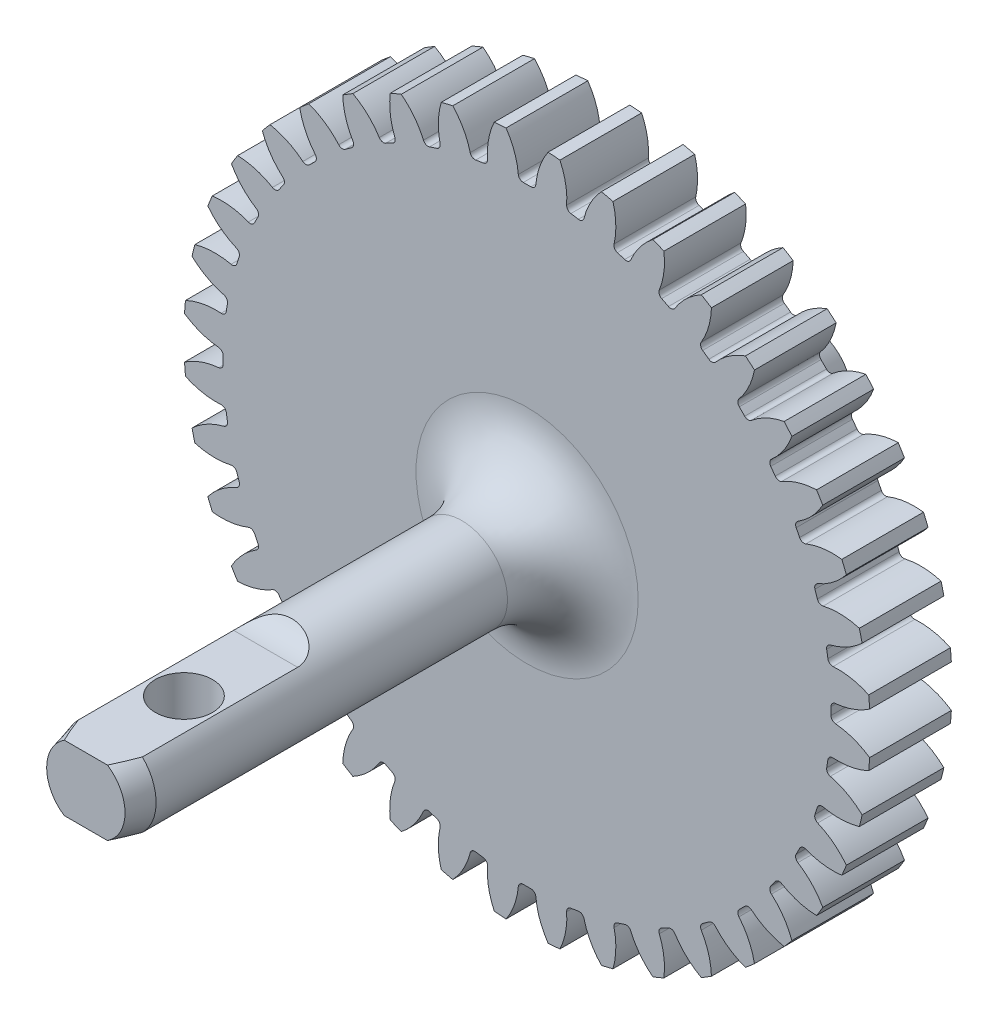
SolidWorks part; units mm, degrees
ref_plane "Front Plane" through (0, 0, 0) normal (0, 0, 1) x (1, 0, 0)
ref_plane "Top Plane" through (0, 0, 0) normal (0, 1, 0) x (1, 0, 0)
ref_plane "Right Plane" through (0, 0, 0) normal (1, 0, 0) x (0, 0, -1)
sketch "Sketch1" plane through (0, 0, 0) normal (0, 0, 1) x (1, 0, 0)
  circle A2 centre (0, 0) radius 20
  circle A3 centre (0, 0) radius 21
  circle A4 centre (0, 0) radius 18.6
  dimension "D1" = 40
  dimension "D2" = 42
  dimension "D3" = 2.4
extrude "Boss-Extrude1" add sketch "Sketch1" along normal mid plane 5 contours A3
sketch "Sketch3" plane through (0, 0, 2.5) normal (0, 0, 1) x (1, 0, 0)
  line L0 (0, 0) -> (0, 21) construction
  line L1 (-0.7852, 19.9846) -> (0.7852, 19.9846) construction
  line L2 (0, 0) -> (-0.5197, 18.5927) construction
  line L3 (0, 17.8273) -> (-1.5001, 21.9488) construction
  line L4 (0, 0) -> (1.6476, 20.9353) construction
  line L5 (0.7852, 19.9846) -> (2.3507, 19.8614) construction
  circle A0 centre (0, 0) radius 21 construction
  arc A1 (-2.1396, 21.8957) -> (-0.5197, 18.5927) centre (-4.9494, 18.4689) cw
  arc A2 (2.1396, 21.8957) -> (0.5197, 18.5927) centre (4.9494, 18.4689) ccw
  circle A3 centre (0, 0) radius 18.6 construction
  arc A4 (0.5197, 18.5927) -> (-0.5197, 18.5927) centre (0, 0) ccw
  circle A5 centre (0, 0) radius 20 construction
  circle A6 centre (0, 0) radius 21 construction
  circle A7 centre (0, 0) radius 22
  arc A8 (2.1396, 21.8957) -> (-2.1396, 21.8957) centre (0, 0) ccw
  dimension "D2" = 20
  dimension "D3" = 4.5
extrude "Cut-Extrude1" cut sketch "Sketch3" against normal through all both and the other way through all
fillet "Fillet1" radius 0.3 2 edges at (0.5197, 18.5927, 0) (-0.5197, 18.5927, 0)
pattern_circular "CirPattern1" count 40 over 360 about axis through (0, 0, 2.5) along (0, 0, -1) of "Cut-Extrude1", "Fillet1"
sketch "Sketch4" plane through (0, 0, 2.5) normal (0, 0, 1) x (1, 0, 0)
  circle A0 centre (0, 0) radius 2.8
  dimension "D1" = 5.6
extrude "Boss-Extrude2" add sketch "Sketch4" along normal blind 27
sketch "Sketch5" plane through (0, 0, -2.5) normal (0, 0, -1) x (-1, 0, 0)
  circle A0 centre (0, 0) radius 2.8
  dimension "D1" = 5.6
extrude "Boss-Extrude3" add sketch "Sketch5" along normal blind 12.43
fillet "Fillet3" radius 7.4 1 edges at (2.8, 0, -2.5)
chamfer "Chamfer1" distance 1.5 angle 15 1 edges at (-2.8, 0, -14.93) first distance on face at (2.8, 0, -9.9)
fillet "Fillet4" radius 4 1 edges at (2.8, 0, 2.5)
chamfer "Chamfer2" distance 1.5 angle 15 1 edges at (2.8, 0, 29.5) first distance on face at (2.8, 0, 6.5)
sketch "Sketch6" plane through (0, 0, 29.5) normal (0, 0, 1) x (1, 0, 0)
  line L0 (-2.8, 0) -> (2.8, 0) construction
  line L1 (-1.9596, -2) -> (1.9596, -2)
  line L2 (-1.9596, 2) -> (1.9596, 2)
  line L3 (-2.8, 2) -> (2.8, 2) construction
  line L4 (-2.8, -2) -> (2.8, -2) construction
  arc A0 (1.9596, 2) -> (-1.9596, 2) centre (0, 0) ccw
  circle A3 centre (0, 0) radius 2.8
  arc A4 (-1.9596, -2) -> (1.9596, -2) centre (0, 0) ccw
  dimension "D1" = 2
  dimension "D2" = 0
  dimension "D3" = 2
extrude "Cut-Extrude2" cut sketch "Sketch6" against normal blind 13
sketch "Sketch7" plane through (0, 2, 0) normal (0, 1, 0) x (1, 0, 0)
  line L0 (-1.9596, -16.5) -> (1.9596, -16.5) construction
  circle A0 centre (0, -23.5) radius 1.75
  dimension "D1" = 3.5
  dimension "D2" = 7
extrude "Cut-Extrude3" cut sketch "Sketch7" against normal blind 11
fillet "Fillet5" radius 2 2 edges at (0, -2, 16.5) (0, 2, 16.5)
equation "\"Module\"= 1mm"
equation "\"Number of Teeth\"= 40"
equation "\"D1@Sketch1\"=\"Module\" * \"Number of Teeth\""
equation "\"D2@Sketch1\"=(\"Number of Teeth\" + 2) * \"Module\""
equation "\"D3@Sketch1\"=\"Module\" * if( \"Module\"=>1.25,2.25,2.4)"
equation "\"D3@Sketch3\"=180 / \"Number of Teeth\""
equation "\"D1@Fillet1\"=0.3 * \"Module\""
equation "\"D1@CirPattern1\"=\"Number of Teeth\""
